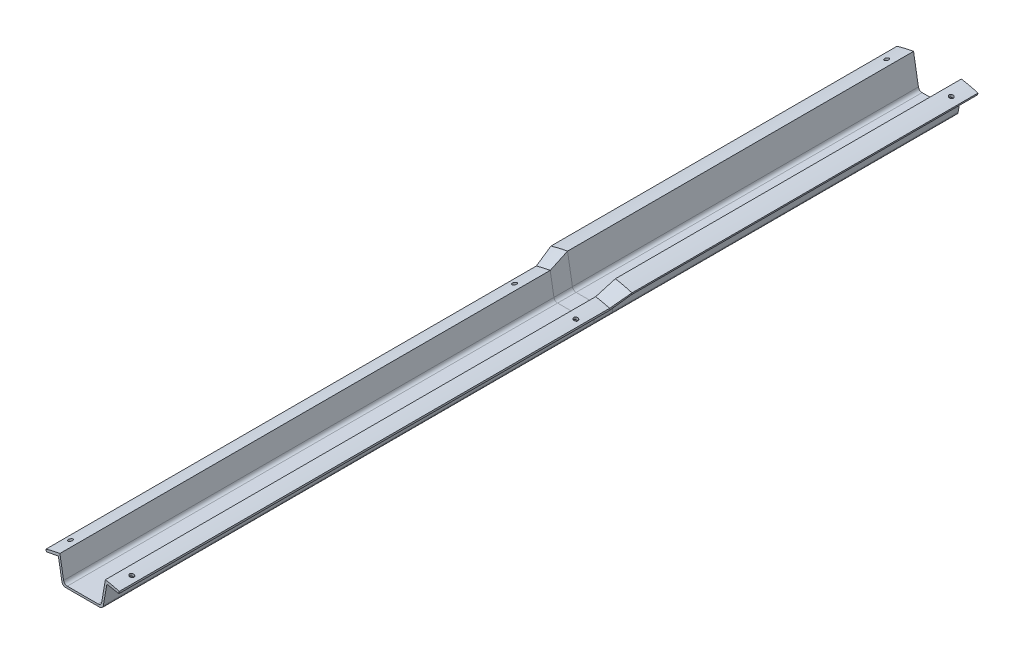
SolidWorks part; units mm, degrees
note: '?' marks a value the reader was unsure of. The reader was unsure of these and kept them because the rebuilt part matched: shared geometry of "Sketch1<4>", "3DSketch1<4>".
material "Hexcel AS4C (3000 Filaments)"
ref_plane "Front Plane" through (0, 0, 0) normal (0, 0, 1) x (1, 0, 0)
ref_plane "Top Plane" through (0, 0, 0) normal (0, 1, 0) x (1, 0, 0)
ref_plane "Right Plane" through (0, 0, 0) normal (1, 0, 0) x (0, 0, -1)
sketch "Sketch1" plane through (0, 0, 0) normal (0, 0, 1) x (1, 0, 0)
  line L0 (0, 0) -> (0, 96.8375) construction
  line L1 (0, 96.8375) -> (0, 73.8464) construction
  line L2 (-12.7, 73.8464) -> (12.7, 73.8464)
  line L3 (12.7, 73.8464) -> (16.413, 95.4364)
  line L4 (-13.843, 72.439) -> (13.843, 72.439)
  line L5 (13.843, 72.439) -> (17.4031, 93.14)
  line L6 (17.4031, 93.14) -> (27.4161, 91.418)
  line L7 (27.4161, 91.418) -> (27.8174, 92.7561)
  line L8 (-27.4161, 91.418) -> (-27.8174, 92.7561)
  line L9 (-17.4031, 93.14) -> (-27.4161, 91.418)
  line L10 (-12.7, 73.8464) -> (-16.413, 95.4364)
  line L11 (-13.843, 72.439) -> (-17.4031, 93.14)
  line L12 (0, 0) -> (22.1558, 94.2689) construction
  line L13 (22.1558, 94.2689) -> (-22.1558, 94.2689) construction
  line L14 (-22.1558, 94.2689) -> (0, 0) construction
  circle A0 centre (0, 0) radius 96.8375 construction
  arc A1 (16.413, 95.4364) -> (27.8174, 92.7561) centre (0, 0) cw
  arc A2 (-16.413, 95.4364) -> (-27.8174, 92.7561) centre (0, 0) ccw
  point P13 (22.4096, 92.279)
  point P16 (-22.4096, 92.279)
  point P21 (0, 72.439)
  dimension "D1" = 21.59
  dimension "D4" = 27.686
  dimension "D3" = 193.675
  dimension "D2" = 25.4
  dimension "D5" = 10.16
  dimension "D6" = 20.701
  dimension "D7" = 1.397
  dimension "D8" = 26.452
sketch3d "3DSketch1"
  line L0 (0, 96.8375, 0) -> (0, 92.075, 12.7) construction
  line L1 (0, 0, 0) -> (0, 0, 12.7) construction
  line L2 (25.1409, 88.5762, 12.7) -> (24.8931, 87.0725, 12.7)
  line L3 (24.8931, 87.0725, 12.7) -> (16.6461, 88.6853, 12.7)
  line L4 (16.6461, 88.6853, 12.7) -> (13.843, 72.4405, 12.7)
  line L5 (0, 92.075, 12.7) -> (0, 0, 12.7) construction
  line L6 (15.6128, 90.7417, 12.7) -> (12.7, 73.8434, 12.7)
  line L7 (12.7, 73.8434, 12.7) -> (-12.7, 73.8434, 12.7)
  line L8 (13.843, 72.4405, 12.7) -> (-13.843, 72.4405, 12.7)
  line L9 (0, 72.439, 0) -> (0, 72.4405, 12.7) construction
  line L10 (-25.1409, 88.5762, 12.7) -> (-24.8931, 87.0725, 12.7)
  line L11 (-24.8931, 87.0725, 12.7) -> (-16.6461, 88.6853, 12.7)
  line L12 (-15.6128, 90.7417, 12.7) -> (-12.7, 73.8434, 12.7)
  line L13 (-16.6461, 88.6853, 12.7) -> (-13.843, 72.4405, 12.7)
  circle A0 centre (0, 0, 12.7) radius 92.075 construction
  arc A1 (15.6128, 90.7417, 12.7) -> (25.1409, 88.5762, 12.7) centre (0, 0, 12.7) cw
  arc A2 (-25.1409, 88.5762, 12.7) -> (-15.6128, 90.7417, 12.7) centre (0, 0, 12.7) ccw
  point P7 (0, 0, 104.775)
  point P17 (0, 0, -79.375)
  point P31 (0, 73.8434, 12.7)
  dimension "D1" = 184.15
  dimension "D10" = 9.7712
  dimension "D2" = 27.686
  dimension "D3" = 17.1474
  dimension "D8" = 99.78
  dimension "D4" = 8.4032
  dimension "D5" = 25.4
  dimension "D6" = 12.7
  dimension "D7" = 1.524
  dimension "D9" = 16.4849
loft "Loft2" add profiles "3DSketch1", "Sketch1"
extrude "Boss-Extrude1" add sketch "Sketch1<4>" against normal blind 237.49
sketch "Sketch1<4>" plane through (0, 0, 0) normal (0, 0, 1) x (1, 0, 0) same geometry as "Sketch1"
extrude "Boss-Extrude2" add sketch "3DSketch1<4>" along direction (0, 0, -1) on the side against the normal blind 336.55
sketch3d "3DSketch1<4>" same geometry as "3DSketch1"
fillet "Fillet1" radius 2.54 6 edges
fillet "Fillet2" radius 2.54 6 edges
sketch "Sketch2" [suppressed] plane through (-17.3185, 88.5538, 0) normal (0.1919, -0.9814, 0) x (-0.9814, -0.1919, 0)
  line L0 (-0.6851, -349.25) -> (7.7181, -349.25) construction
  line L1 (3.5165, -336.55) -> (-0.6851, -336.55) construction
  line L2 (-0.6851, -12.7) -> (-0.6851, -349.25) construction
  line L3 (3.5165, -336.55) -> (7.7181, -336.55) construction
  line L4 (7.7181, -12.7) -> (7.7181, -349.25) construction
  line L5 (-0.6851, -31.75) -> (3.5165, -31.75) construction
  line L6 (3.5165, -31.75) -> (7.7181, -31.75) construction
  point P0 (3.5165, -336.55)
  point P14 (3.5165, -31.75)
  dimension "D1" = 12.7
  dimension "D2" = 317.5
sketch "Sketch3" [suppressed] plane through (17.3185, 88.5538, 0) normal (-0.1919, -0.9814, 0) x (-0.9814, 0.1919, 0)
  line L0 (-7.7181, -349.25) -> (0.6851, -349.25) construction
  line L1 (-3.5165, -336.55) -> (0.6851, -336.55) construction
  line L2 (0.6851, -12.7) -> (0.6851, -349.25) construction
  line L3 (0.6851, -31.75) -> (-3.5165, -31.75) construction
  line L4 (-3.5165, -31.75) -> (-7.7181, -31.75) construction
  line L5 (-3.5165, -336.55) -> (-7.7181, -336.55) construction
  line L6 (-7.7181, -12.7) -> (-7.7181, -349.25) construction
  point P0 (-3.5165, -336.55)
  point P14 (-3.5165, -31.75)
  dimension "D1" = 12.7
  dimension "D2" = 317.5
hole_wizard "#4 Clearance Hole1" [suppressed] positions "Sketch4" profile "Sketch5" hole size "#4" standard "ANSI Inch"
sketch "Sketch4" [suppressed] plane through (-17.3185, 88.5538, 0) normal (0.1919, -0.9814, 0) x (-0.9814, -0.1919, 0)
  point P0 (3.5165, -336.55)
  point P3 (3.5165, -31.75)
sketch "Sketch5" [suppressed] plane through (-20.7696, 87.8789, 336.55) normal (0, 0, 1) x (0.9814, 0.1919, 0)
  line L0 (0, 0) -> (0, 8.7699)
  line L1 (0, 8.7699) -> (1.4732, 8.7699)
  line L2 (1.4732, 8.7699) -> (1.4732, 0)
  line L5 (1.4732, 0) -> (0, 0)
  line L11 (0, -6.35) -> (0, 107.95) construction
  dimension "Thru Hole Dia." = 2.9464
  dimension "Thru Hole Depth" = 8.7699
hole_wizard "#4 Clearance Hole2" [suppressed] positions "Sketch6" profile "Sketch7" hole size "#4" standard "ANSI Inch"
sketch "Sketch6" [suppressed] plane through (17.3185, 88.5538, 0) normal (-0.1919, -0.9814, 0) x (-0.9814, 0.1919, 0)
  point P0 (-3.5165, -336.55)
  point P4 (-3.5165, -31.75)
sketch "Sketch7" plane through (20.7696, 87.8789, 336.55) normal (0, 0, 1) x (0.9814, -0.1919, 0)
  line L0 (0, 0) -> (0, 8.7699)
  line L1 (0, 8.7699) -> (1.4732, 8.7699)
  line L2 (1.4732, 8.7699) -> (1.4732, 0)
  line L5 (1.4732, 0) -> (0, 0)
  line L11 (0, -6.35) -> (0, 107.95) construction
  dimension "Thru Hole Dia." = 2.9464
  dimension "Thru Hole Depth" = 8.7699
ref_axis "Axis1" [suppressed] through (21.2433, 90.3007, 336.55) along (-0.1919, -0.9814, 0)?
ref_axis "Axis2" [suppressed] through (-21.1219, 89.6803, 336.55) along (0.1919, -0.9814, 0)?
ref_axis "Axis3" through (0, 0, -275.0304) along (0, 0, 1)?
ref_plane "Plane1" through (0, 0, 0) normal (0.9735, 0.2288, 0) x (0, 0, 1)
ref_plane "Plane3" through (0, 0, 0) normal (0.9735, -0.2288, 0) x (0, 0, 1)
ref_plane "Plane4" through (-21.0645, 89.6331, 0) normal (-0.2288, 0.9735, 0) x (0.9735, 0.2288, 0)
ref_plane "Plane5" through (21.0645, 89.6331, 0) normal (0.2288, 0.9735, 0) x (0.9735, -0.2288, 0)
sketch "Sketch8" plane through (-21.0645, 89.6331, 0) normal (-0.2288, 0.9735, 0) x (0.9735, 0.2288, 0)
  line L0 (0, -89.4018) -> (0, 89.4018) construction
  line L1 (0, 275.0304) -> (0, -409.7154) construction
  line L2 (-4.2101, -349.25) -> (5.5608, -349.25) construction
  point P0 (0, -336.55)
  point P1 (0, -31.75)
  dimension "D1" = 12.7
  dimension "D2" = 317.5
sketch "Sketch9" plane through (21.0645, 89.6331, 0) normal (0.2288, 0.9735, 0) x (0.9735, -0.2288, 0)
  line L0 (0, -90.9887) -> (0, 90.9887) construction
  line L1 (-5.5608, -349.25) -> (4.2101, -349.25) construction
  point P0 (0, -336.55)
  point P1 (0, -31.75)
  dimension "D1" = 12.7
  dimension "D2" = 317.5
hole_wizard "#4 Clearance Hole3" positions "Sketch10" profile "Sketch12" hole size "#4" standard "ANSI Inch"
sketch "Sketch10" plane through (21.0645, 89.6331, 0) normal (0.2288, 0.9735, 0) x (0.9735, -0.2288, 0)
  point P0 (0, -336.55)
  point P3 (0, -31.75)
sketch "Sketch12" plane through (21.0645, 89.6331, 336.55) normal (0, 0, 1) x (-0.9735, 0.2288, 0)
  line L0 (0, 0) -> (0, 26.2852)
  line L1 (0, 26.2852) -> (1.4732, 25.4)
  line L2 (1.4732, 25.4) -> (1.4732, 0)
  line L5 (1.4732, 0) -> (0, 0)
  line L10 (0, 26.2852) -> (-1.4732, 25.4) construction
  line L11 (0, -6.35) -> (0, 107.95) construction
  dimension "Hole Dia." = 2.9464
  dimension "Hole Depth" = 25.4
  dimension "Drill Angle" = 118
hole_wizard "#4 Clearance Hole4" positions "Sketch13" profile "Sketch14" hole size "#4" standard "ANSI Inch"
sketch "Sketch13" plane through (-21.0645, 89.6331, 0) normal (-0.2288, 0.9735, 0) x (0.9735, 0.2288, 0)
  point P0 (0, -336.55)
  point P3 (0, -31.75)
sketch "Sketch14" plane through (-21.0645, 89.6331, 336.55) normal (0, 0, 1) x (-0.9735, -0.2288, 0)
  line L0 (0, 0) -> (0, 26.2852)
  line L1 (0, 26.2852) -> (1.4732, 25.4)
  line L2 (1.4732, 25.4) -> (1.4732, 0)
  line L5 (1.4732, 0) -> (0, 0)
  line L10 (0, 26.2852) -> (-1.4732, 25.4) construction
  line L11 (0, -6.35) -> (0, 107.95) construction
  dimension "Hole Dia." = 2.9464
  dimension "Hole Depth" = 25.4
  dimension "Drill Angle" = 118
ref_axis "Axis4" through (-20.6908, 88.0427, 336.55) along (-0.2288, 0.9735, 0)?
ref_axis "Axis5" through (20.5187, 87.3105, 336.55) along (0.2288, 0.9735, 0)?
ref_plane "Plane6" through (-22.1541, 94.2693, 0) normal (-0.2288, 0.9735, 0) x (0.9735, 0.2288, 0)
ref_plane "Plane7" through (22.1541, 94.2693, 0) normal (0.2288, 0.9735, 0) x (0.9735, -0.2288, 0)
sketch "Sketch15" plane through (22.1541, 94.2693, 0) normal (0.2288, 0.9735, 0) x (0.9735, -0.2288, 0)
  line L0 (0, -90.9887) -> (0, 90.9887) construction
  line L1 (5.8594, 237.49) -> (-5.8558, 237.49) construction
  point P0 (0, 224.79)
  dimension "D1" = 12.7
sketch "Sketch16" plane through (-22.1541, 94.2693, 0) normal (-0.2288, 0.9735, 0) x (0.9735, 0.2288, 0)
  line L0 (0, -89.4018) -> (0, 89.4018) construction
  line L1 (0, 275.0304) -> (0, -409.7154) construction
  line L2 (5.8558, 237.49) -> (-5.8594, 237.49) construction
  point P0 (0, 224.79)
  dimension "D1" = 12.7
hole_wizard "#4 Clearance Hole5" positions "Sketch19" profile "Sketch18" hole size "#4" standard "ANSI Inch"
sketch "Sketch19" plane through (-22.1541, 94.2693, 0) normal (-0.2288, 0.9735, 0) x (0.9735, 0.2288, 0)
  point P0 (0, 224.79)
sketch "Sketch18" plane through (-22.1541, 94.2693, -224.79) normal (0, 0, 1) x (-0.9735, -0.2288, 0)
  line L0 (0, 0) -> (0, 13.5852)
  line L1 (0, 13.5852) -> (1.4732, 12.7)
  line L2 (1.4732, 12.7) -> (1.4732, 0)
  line L5 (1.4732, 0) -> (0, 0)
  line L10 (0, 13.5852) -> (-1.4732, 12.7) construction
  line L11 (0, -6.35) -> (0, 107.95) construction
  dimension "Hole Dia." = 2.9464
  dimension "Hole Depth" = 12.7
  dimension "Drill Angle" = 118
hole_wizard "#4 Clearance Hole6" positions "Sketch20" profile "Sketch21" hole size "#4" standard "ANSI Inch"
sketch "Sketch20" plane through (22.1541, 94.2693, 0) normal (0.2288, 0.9735, 0) x (0.9735, -0.2288, 0)
  point P0 (0, 224.79)
sketch "Sketch21" plane through (22.1541, 94.2693, -224.79) normal (0, 0, 1) x (-0.9735, 0.2288, 0)
  line L0 (0, 0) -> (0, 13.5852)
  line L1 (0, 13.5852) -> (1.4732, 12.7)
  line L2 (1.4732, 12.7) -> (1.4732, 0)
  line L5 (1.4732, 0) -> (0, 0)
  line L10 (0, 13.5852) -> (-1.4732, 12.7) construction
  line L11 (0, -6.35) -> (0, 107.95) construction
  dimension "Hole Dia." = 2.9464
  dimension "Hole Depth" = 12.7
  dimension "Drill Angle" = 118
